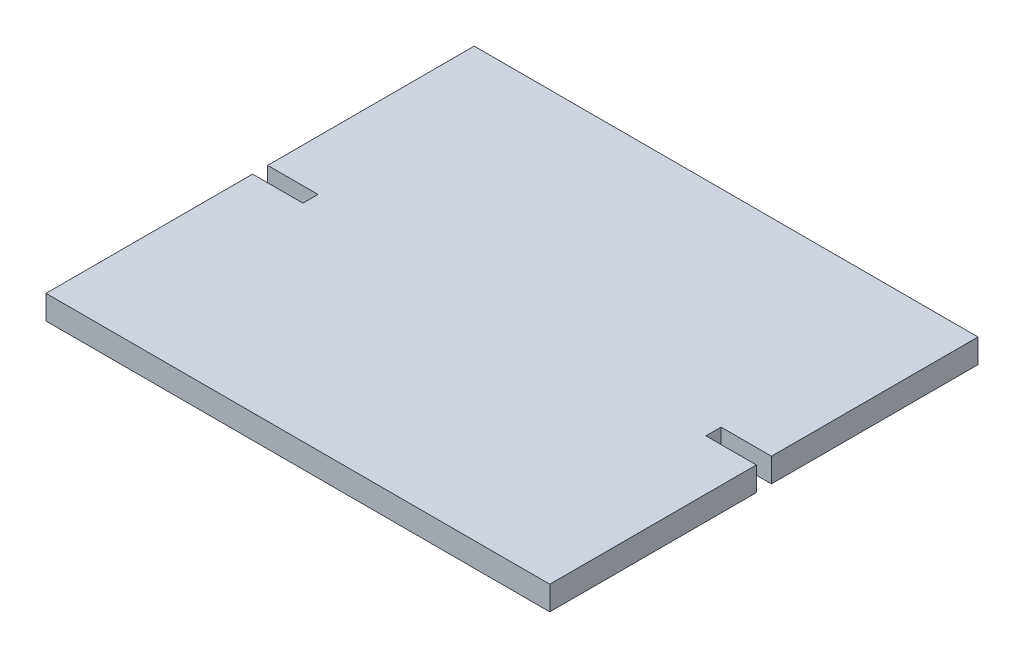
SolidWorks part; units mm, degrees
material "Hardboard"
ref_plane "Front Plane" through (0, 0, 0) normal (0, 0, 1) x (1, 0, 0)
ref_plane "Top Plane" through (0, 0, 0) normal (0, 1, 0) x (1, 0, 0)
ref_plane "Right Plane" through (0, 0, 0) normal (1, 0, 0) x (0, 0, -1)
sketch "Sketch3" plane through (0, 0, 0) normal (0, 1, 0) x (1, 0, 0)
  line L0 (0, -42.5) -> (0, 42.5) construction
  line L1 (-50, -42.5) -> (50, -42.5)
  line L2 (-50, 42.5) -> (-50, 1.5)
  line L3 (-50, 42.5) -> (50, 42.5)
  line L4 (40, 1.5) -> (40, -1.5)
  line L5 (-50, -42.5) -> (50, 42.5) construction
  line L6 (-50, 42.5) -> (50, -42.5) construction
  line L7 (-50, 1.5) -> (-40, 1.5)
  line L8 (-50, -1.5) -> (-50, -42.5)
  line L9 (-50, -1.5) -> (-40, -1.5)
  line L10 (-40, 1.5) -> (-40, -1.5)
  line L11 (50, -1.5) -> (40, -1.5)
  line L12 (50, -1.5) -> (50, -42.5)
  line L13 (50, 1.5) -> (40, 1.5)
  line L14 (50, 42.5) -> (50, 1.5)
  line L15 (-50, -1.5) -> (-50, 1.5) construction
  point P0 (0, 0)
  point P16 (-50, 0)
  point P17 (50, 0)
  dimension "D1" = 85
  dimension "D2" = 100
  dimension "D3" = 3
  dimension "D4" = 10
extrude "Boss-Extrude1" add sketch "Sketch3" against normal blind 4.7625
sketch "Sketch4" [suppressed] plane through (0, 0, 0) normal (1, 0, 0) x (0, 0, -1)
  line L0 (-30, 4.7625) -> (-1.5, 4.7625) construction
  line L1 (-30, 4.7625) -> (-30, 0) construction
  line L2 (-30, 0) -> (-1.5, 0) construction
  line L3 (-30, 4.7625) -> (-1.5, 4.7625)
  line L4 (-30, 4.7625) -> (-30, 0)
  line L5 (-30, 0) -> (-1.5, 0)
  line L6 (-30, 4.7625) -> (-30, -12.1326)
  line L7 (-30, -12.1326) -> (-9.7945, -32.8109)
  line L9 (-9.7945, -32.8109) -> (-7.1756, -30.2519)
  line L11 (-7.1756, -30.2519) -> (-24.8806, -12.1326)
  line L12 (-24.8806, -12.1326) -> (-24.8806, 4.7625)
  line L13 (-24.8806, 4.7625) -> (-30, 4.7625)
